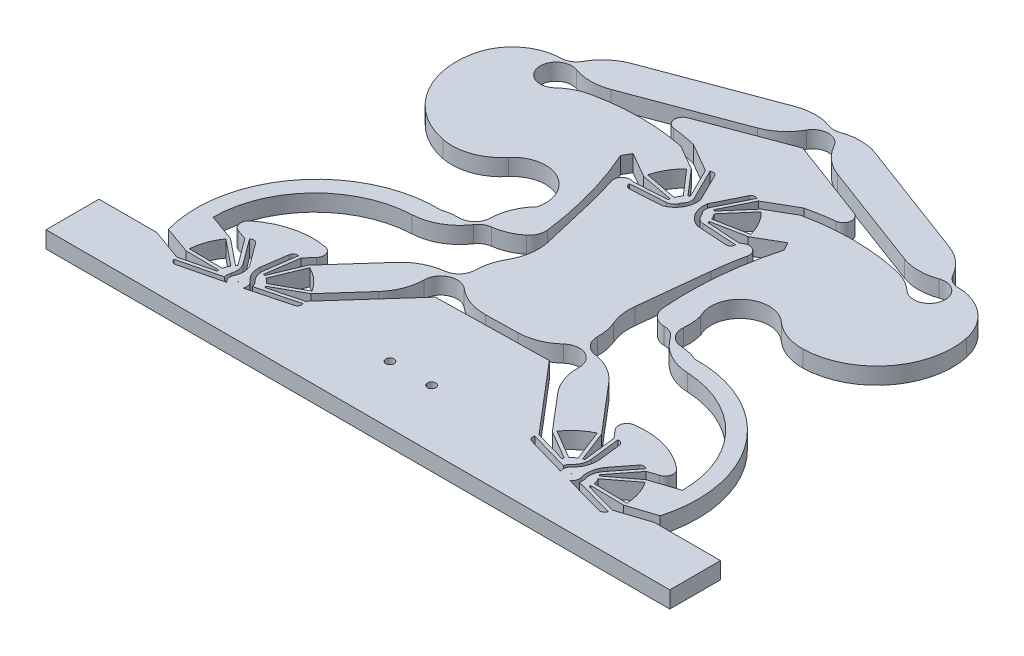
SolidWorks part; units mm, degrees
ref_plane "Front Plane" through (0, 0, 0) normal (0, 0, 1) x (1, 0, 0)
ref_plane "Top Plane" through (0, 0, 0) normal (0, 1, 0) x (1, 0, 0)
ref_plane "Right Plane" through (0, 0, 0) normal (1, 0, 0) x (0, 0, -1)
sketch "Sketch1" plane through (0, 0, 0) normal (0, 1, 0) x (1, 0, 0)
  line L1 (150, 150) -> (-150, 150)
  line L2 (150, 150) -> (150, -150)
  line L3 (150, -150) -> (-150, -150)
  line L4 (-150, 150) -> (-150, -150)
  line L5 (150, 150) -> (-150, -150) construction
  line L6 (150, -150) -> (-150, 150) construction
  point P0 (0, 0)
  dimension "D1" = 300
  dimension "D2" = 300
extrude "Boss-Extrude1" add sketch "Sketch1" along normal blind 10
sketch "Sketch6" plane through (0, 10, 0) normal (0, 1, 0) x (1, 0, 0)
  line L1 (150, 150) -> (187.3693, 150)
  line L2 (150, 150) -> (150, -150)
  line L3 (150, -150) -> (187.3693, -150)
  line L4 (187.3693, 150) -> (187.3693, -150)
extrude "Boss-Extrude2" add sketch "Sketch6" against normal blind 10
sketch "Sketch11" plane through (0, 10, 0) normal (0, 1, 0) x (1, 0, 0)
  line L1 (-150, -150) -> (-230.9434, -150)
  line L2 (-150, -150) -> (-150, 150)
  line L3 (-150, 150) -> (-230.9434, 150)
  line L4 (-230.9434, -150) -> (-230.9434, 150)
extrude "Boss-Extrude3" add sketch "Sketch11" against normal blind 10
sketch "Sketch2" plane through (0, 10, 0) normal (0, 1, 0) x (1, 0, 0)
  line L0 (-102.598, -119.2289) -> (-25.1328, -32.577) construction
  line L1 (-91.6465, -114.3232) -> (-72.2867, -109.3035)
  line L2 (-95.822, -117.472) -> (-71.6953, -111.2163)
  line L3 (-97.9731, -121.129) -> (-73.4342, -114.7664)
  line L4 (-92.1087, -113.4002) -> (-74.6265, -103.6856)
  line L5 (-93.2268, -111.7335) -> (-75.6526, -101.9678)
  line L6 (-74.6265, -103.6856) -> (-63.0561, -90.7431)
  line L7 (-72.2867, -109.3035) -> (-58.9642, -94.4011)
  line L8 (-58.9642, -94.4011) -> (-63.0561, -90.7431)
  line L9 (-82.795, -73.0969) -> (-78.7031, -76.755)
  line L10 (-96.1175, -87.9993) -> (-82.795, -73.0969)
  line L11 (-90.2735, -89.6975) -> (-78.7031, -76.755)
  line L12 (-96.1952, -109.0798) -> (-88.4519, -90.5255)
  line L13 (-97.9763, -108.1546) -> (-90.2735, -89.6975)
  line L14 (-105.0023, -114.8449) -> (-101.4181, -89.7493)
  line L15 (-101.6083, -112.2992) -> (-98.0843, -87.625)
  line L16 (-98.9452, -107.7984) -> (-96.1175, -87.9993)
  arc A0 (-105.0023, -114.8449) -> (-97.9731, -121.129) centre (-102.598, -119.2289) cw
  arc A1 (-97.9326, -114.0103) -> (-95.822, -117.472) centre (-102.598, -119.2289) cw
  arc A2 (-71.6953, -111.2163) -> (-73.4342, -114.7664) centre (-74.3398, -112.1219) cw
  arc A3 (-96.1952, -109.0798) -> (-93.2268, -111.7335) centre (-102.598, -119.2289) cw
  circle A4 centre (-102.598, -119.2289) radius 0.1
  arc A5 (-75.6526, -101.9678) -> (-88.4519, -90.5255) centre (-102.598, -119.2289) ccw
  arc A8 (-92.1087, -113.4002) -> (-91.6465, -114.3232) centre (-102.598, -119.2289) cw
  arc A9 (-97.9763, -108.1546) -> (-98.9452, -107.7984) centre (-102.598, -119.2289) ccw
  arc A11 (-98.0843, -87.625) -> (-101.4181, -89.7493) centre (-98.6891, -90.3541) ccw
  arc A12 (-97.9326, -114.0103) -> (-101.6083, -112.2992) centre (-102.598, -119.2289) ccw
  point P0 (-102.598, -119.2289)
  point P12 (0, -128.9646)
  point P13 (10.2845, -122.7817)
  point P14 (11.9871, -129.5203)
  point P15 (0, -128.9646)
  point P17 (11.9871, -129.5203)
  point P19 (-74.6265, -103.6856)
  dimension "D3" = 7
  dimension "D9" = 20
  dimension "D1" = 3
  dimension "D6" = 20
  dimension "D7" = 2
  dimension "D8" = 2
extrude "Cut-Extrude1" cut sketch "Sketch2" against normal blind 10
sketch "Sketch7" plane through (0, 10, 0) normal (0, 1, 0) x (1, 0, 0)
  line L0 (97.402, -119.2289) -> (22.065, -30.7204) construction
  line L1 (94.028, -107.713) -> (91.6822, -87.8511)
  line L2 (96.581, -112.2772) -> (93.6575, -87.5247)
  line L3 (99.9121, -114.9047) -> (96.9388, -89.7294)
  line L4 (93.0508, -108.0456) -> (85.7987, -89.4067)
  line L5 (91.2477, -108.9272) -> (83.9575, -90.1903)
  line L6 (85.7987, -89.4067) -> (74.5462, -76.1869)
  line L7 (91.6822, -87.8511) -> (78.7257, -72.6294)
  line L8 (78.7257, -72.6294) -> (74.5462, -76.1869)
  line L9 (54.3844, -93.3483) -> (58.5639, -89.7907)
  line L10 (67.3408, -108.57) -> (54.3844, -93.3483)
  line L11 (69.8164, -103.0106) -> (58.5639, -89.7907)
  line L12 (88.2158, -111.508) -> (70.884, -101.3182)
  line L13 (87.0574, -113.147) -> (69.8164, -103.0106)
  line L14 (92.7323, -121.016) -> (68.3553, -114.0592)
  line L15 (90.6708, -117.3079) -> (66.7031, -110.4679)
  line L16 (86.573, -114.0586) -> (67.3408, -108.57)
  circle A0 centre (-102.598, -119.2289) radius 0.1 construction
  arc A1 (92.7323, -121.016) -> (99.9121, -114.9047) centre (97.402, -119.2289) cw
  arc A2 (92.8648, -113.8985) -> (96.581, -112.2772) centre (97.402, -119.2289) cw
  arc A3 (93.6575, -87.5247) -> (96.9388, -89.7294) centre (94.1958, -90.2676) cw
  arc A4 (88.2158, -111.508) -> (91.2477, -108.9272) centre (97.402, -119.2289) cw
  circle A5 centre (97.402, -119.2289) radius 0.1
  arc A6 (83.9575, -90.1903) -> (70.884, -101.3182) centre (97.402, -119.2289) ccw
  arc A7 (93.0508, -108.0456) -> (94.028, -107.713) centre (97.402, -119.2289) cw
  arc A8 (87.0574, -113.147) -> (86.573, -114.0586) centre (97.402, -119.2289) ccw
  arc A9 (66.7031, -110.4679) -> (68.3553, -114.0592) centre (69.3248, -111.4374) ccw
  arc A10 (92.8648, -113.8985) -> (90.6708, -117.3079) centre (97.402, -119.2289) ccw
  point P0 (97.402, -119.2289)
  point P3 (97.402, -119.2289)
  point P15 (85.7987, -89.4067)
  dimension "D1" = 200
extrude "Cut-Extrude5" cut sketch "Sketch7" against normal blind 10
sketch "Sketch9" plane through (0, 10, 0) normal (0, 1, 0) x (1, 0, 0)
  line L0 (-4.298, 51.3626) -> (-4.2901, -64.8674) construction
  line L1 (-9.1923, 40.406) -> (-20.2788, 23.76)
  line L2 (-8.1783, 45.5365) -> (-21.9946, 24.7917)
  line L3 (-9.0122, 49.6964) -> (-23.0645, 28.5973)
  line L4 (-8.2325, 40.0259) -> (-14.79, 21.1315)
  line L5 (-6.288, 39.5287) -> (-12.88, 20.5348)
  line L6 (-14.79, 21.1315) -> (-14.7888, 3.7711)
  line L7 (-20.2788, 23.76) -> (-20.2774, 3.7708)
  line L8 (-20.2774, 3.7708) -> (-14.7888, 3.7711)
  line L9 (11.6878, 3.7729) -> (6.1992, 3.7726)
  line L10 (11.6865, 23.7622) -> (11.6878, 3.7729)
  line L11 (6.198, 21.1329) -> (6.1992, 3.7726)
  line L12 (-2.3064, 39.529) -> (4.2882, 20.536)
  line L13 (-0.362, 40.0265) -> (6.198, 21.1329)
  line L14 (0.4164, 49.697) -> (14.4715, 28.5999)
  line L15 (-0.417, 45.537) -> (13.4022, 24.7941)
  line L16 (0.5977, 40.4067) -> (11.6865, 23.7622)
  arc A0 (0.4164, 49.697) -> (-9.0122, 49.6964) centre (-4.298, 51.3626) cw
  arc A2 (-4.2975, 44.3626) -> (-8.1783, 45.5365) centre (-4.298, 51.3626) cw
  arc A3 (-21.9946, 24.7917) -> (-23.0645, 28.5973) centre (-20.6267, 27.2295) cw
  arc A4 (-2.3064, 39.529) -> (-6.288, 39.5287) centre (-4.298, 51.3626) cw
  circle A5 centre (-4.298, 51.3626) radius 0.1
  arc A6 (-12.88, 20.5348) -> (4.2882, 20.536) centre (-4.298, 51.3626) ccw
  arc A7 (-8.2325, 40.0259) -> (-9.1923, 40.406) centre (-4.298, 51.3626) cw
  arc A8 (-0.362, 40.0265) -> (0.5977, 40.4067) centre (-4.298, 51.3626) ccw
  arc A9 (13.4022, 24.7941) -> (14.4715, 28.5999) centre (12.034, 27.2317) ccw
  arc A10 (-4.2975, 44.3626) -> (-0.417, 45.537) centre (-4.298, 51.3626) ccw
  point P1 (-4.298, 51.3626)
  point P6 (-4.298, 51.3626)
  point P14 (-14.79, 21.1315)
extrude "Cut-Extrude7" cut sketch "Sketch9" against normal blind 10
sketch "Sketch8" plane through (0, 10, 0) normal (0, 1, 0) x (1, 0, 0)
  line L0 (-78.7031, -76.755) -> (-54.1381, -49.2767)
  line L1 (-82.795, -73.0969) -> (-20.2788, -3.1667)
  line L2 (54.3844, -93.3483) -> (31.8171, -66.8354)
  line L3 (58.5639, -89.7907) -> (40.7844, -68.9027)
  line L4 (74.5462, -76.1869) -> (50.3154, -47.7198)
  line L5 (78.7257, -72.6294) -> (11.6865, 6.1307)
  line L6 (-63.0561, -90.7431) -> (-44.4632, -69.9452)
  line L7 (-58.9642, -94.4011) -> (-35.4517, -68.1002)
  line L8 (78.7257, -72.6294) -> (74.5462, -76.1869) construction
  line L9 (58.5639, -89.7907) -> (54.3844, -93.3483) construction
  line L10 (-58.9642, -94.4011) -> (-63.0561, -90.7431) construction
  line L11 (-78.7031, -76.755) -> (-82.795, -73.0969) construction
  line L12 (78.7257, -72.6294) -> (74.5462, -76.1869)
  line L13 (58.5639, -89.7907) -> (54.3844, -93.3483)
  line L14 (-58.9642, -94.4011) -> (-63.0561, -90.7431)
  line L15 (-78.7031, -76.755) -> (-82.795, -73.0969)
  line L16 (-102.598, -119.3289) -> (-42.6146, -52.232) construction
  line L17 (97.502, -119.2289) -> (39.1666, -50.6944) construction
  line L18 (-63.0561, -90.7431) -> (-74.6265, -103.6856) construction
  line L19 (69.8164, -103.0106) -> (58.5639, -89.7907) construction
  line L20 (-42.6146, -52.232) -> (39.1666, -50.6944) construction
  line L21 (-27.7984, -62.4553) -> (24.3044, -61.4757)
  line L22 (-35.4517, -68.1002) -> (31.8171, -66.8354)
  line L23 (-42.4172, -62.7302) -> (39.364, -61.1926) construction
  line L24 (-82.795, -73.0969) -> (-96.1175, -87.9993) construction
  line L25 (-42.3138, -68.2292) -> (39.4673, -66.6916) construction
  line L26 (-90.2735, -89.6975) -> (-78.7031, -76.755) construction
  line L27 (91.6822, -87.8511) -> (78.7257, -72.6294) construction
  line L28 (-20.2788, -3.1667) -> (-20.2774, 3.7708)
  line L29 (-20.2774, 3.7708) -> (-14.7888, 3.7711)
  line L30 (-14.7888, 3.7711) -> (-14.79, -5.2622)
  line L31 (6.1992, 4.1095) -> (11.6865, 6.1307)
  line L32 (-47.4733, -41.8215) -> (43.8337, -40.1048) construction
  line L33 (-40.8084, -34.3663) -> (-14.79, -5.2622)
  line L34 (37.352, -32.4899) -> (6.1992, 4.1095)
  circle A0 centre (-102.598, -119.2289) radius 0.1 construction
  circle A1 centre (97.402, -119.2289) radius 0.1 construction
  arc A2 (-44.4632, -69.9452) -> (-27.7984, -62.4553) centre (-37.7984, -62.49) cw
  arc A3 (40.7844, -68.9027) -> (24.3044, -61.4757) centre (34.3026, -61.2877) ccw
  arc A4 (-40.8084, -34.3663) -> (-54.1381, -49.2767) centre (-47.4733, -41.8215) cw
  arc A5 (50.3154, -47.7198) -> (37.352, -32.4899) centre (43.8337, -40.1048) cw
  dimension "D5" = 10
  dimension "D6" = 10
  dimension "D8" = 10
  dimension "D9" = 10
  dimension "D1" = 90
  dimension "D2" = 90
  dimension "D7" = 10.5
  dimension "D3" = 10.5
  dimension "D4" = 16
extrude "Cut-Extrude6" cut sketch "Sketch8" against normal blind 10
sketch "Sketch10" plane through (0, 10, 0) normal (0, 1, 0) x (1, 0, 0)
  line L0 (-102.598, -119.2289) -> (-211.9592, -79.8648) construction
  line L1 (-111.2489, -110.9126) -> (-123.1554, -94.8429)
  line L2 (-106.7653, -113.6045) -> (-121.6035, -93.578)
  line L3 (-102.5688, -114.229) -> (-117.6605, -93.8604)
  line L4 (-111.9317, -111.6869) -> (-127.4878, -99.1168)
  line L5 (-113.0581, -113.348) -> (-128.6962, -100.7118)
  line L6 (-127.4878, -99.1168) -> (-143.8223, -93.2373)
  line L7 (-123.1554, -94.8429) -> (-141.9634, -88.0731)
  line L8 (-141.9634, -88.0731) -> (-143.8223, -93.2373)
  line L9 (-152.7892, -118.1493) -> (-150.9303, -112.985)
  line L10 (-133.9812, -124.9191) -> (-152.7892, -118.1493)
  line L11 (-134.5959, -118.8645) -> (-150.9303, -112.985)
  line L12 (-114.4066, -117.0943) -> (-134.5106, -116.8653)
  line L13 (-114.5972, -119.0923) -> (-134.5959, -118.8645)
  line L14 (-105.7621, -123.1004) -> (-130.373, -129.1782)
  line L15 (-109.3938, -120.9072) -> (-133.5915, -126.8829)
  line L16 (-114.5646, -120.124) -> (-133.9812, -124.9191)
  line L17 (97.402, -119.2289) -> (207.8148, -82.9187) construction
  line L18 (109.3391, -120.4562) -> (128.615, -125.7889)
  line L19 (104.1486, -121.0954) -> (128.1709, -127.7412)
  line L20 (100.4573, -123.1869) -> (124.8898, -129.9462)
  line L21 (109.4004, -119.4257) -> (129.3977, -119.7537)
  line L22 (109.2654, -117.4232) -> (129.368, -117.753)
  line L23 (129.3977, -119.7537) -> (145.8892, -114.3304)
  line L24 (128.615, -125.7889) -> (147.6038, -119.5443)
  line L25 (147.6038, -119.5443) -> (145.8892, -114.3304)
  line L26 (137.6179, -89.1789) -> (139.3326, -94.3928)
  line L27 (118.6291, -95.4235) -> (137.6179, -89.1789)
  line L28 (122.8411, -99.8162) -> (139.3326, -94.3928)
  line L29 (108.0215, -113.6409) -> (124.0046, -101.4441)
  line L30 (106.9417, -111.9491) -> (122.8411, -99.8162)
  line L31 (97.5118, -114.2301) -> (113.1636, -94.2888)
  line L32 (101.724, -113.7225) -> (117.1129, -94.116)
  line L33 (106.2807, -111.1562) -> (118.6291, -95.4235)
  arc A0 (-105.7621, -123.1004) -> (-102.5688, -114.229) centre (-102.598, -119.2289) cw
  arc A1 (-109.1843, -116.8582) -> (-106.7653, -113.6045) centre (-102.598, -119.2289) cw
  arc A2 (-121.6035, -93.578) -> (-117.6605, -93.8604) centre (-119.7732, -95.6907) cw
  arc A3 (-114.4066, -117.0943) -> (-113.0581, -113.348) centre (-102.598, -119.2289) cw
  circle A4 centre (-102.598, -119.2289) radius 0.1
  arc A5 (-128.6962, -100.7118) -> (-134.5106, -116.8653) centre (-102.598, -119.2289) ccw
  arc A6 (-111.9317, -111.6869) -> (-111.2489, -110.9126) centre (-102.598, -119.2289) cw
  arc A7 (-114.5972, -119.0923) -> (-114.5646, -120.124) centre (-102.598, -119.2289) ccw
  arc A8 (-133.5915, -126.8829) -> (-130.373, -129.1782) centre (-130.8346, -126.4213) ccw
  arc A9 (-109.1843, -116.8582) -> (-109.3938, -120.9072) centre (-102.598, -119.2289) ccw
  arc A10 (97.5118, -114.2301) -> (100.4573, -123.1869) centre (97.402, -119.2289) cw
  arc A11 (104.0517, -117.0421) -> (104.1486, -121.0954) centre (97.402, -119.2289) cw
  arc A12 (128.1709, -127.7412) -> (124.8898, -129.9462) centre (125.4278, -127.2031) cw
  arc A13 (108.0215, -113.6409) -> (109.2654, -117.4232) centre (97.402, -119.2289) cw
  circle A14 centre (97.402, -119.2289) radius 0.1
  arc A15 (129.368, -117.753) -> (124.0046, -101.4441) centre (97.402, -119.2289) ccw
  arc A16 (109.4004, -119.4257) -> (109.3391, -120.4562) centre (97.402, -119.2289) cw
  arc A17 (106.9417, -111.9491) -> (106.2807, -111.1562) centre (97.402, -119.2289) ccw
  arc A18 (117.1129, -94.116) -> (113.1636, -94.2888) centre (115.2247, -96.177) ccw
  arc A19 (104.0517, -117.0421) -> (101.724, -113.7225) centre (97.402, -119.2289) ccw
  point P0 (-102.598, -119.2289)
  point P12 (-127.4878, -99.1168)
  point P33 (-102.598, -119.2289)
  point P34 (97.402, -119.2289)
  point P36 (97.402, -119.2289)
  point P50 (129.3977, -119.7537)
extrude "Cut-Extrude8" cut sketch "Sketch10" against normal blind 10
sketch "Sketch12" plane through (0, 10, 0) normal (0, 1, 0) x (1, 0, 0)
  line L0 (-4.298, 51.3626) -> (96.3562, 109.4844) construction
  line L1 (7.6378, 52.6023) -> (27.5969, 51.3241)
  line L2 (2.6877, 50.9152) -> (27.5613, 49.3223)
  line L3 (1.8219, 47.9645) -> (24.8005, 46.493)
  line L4 (7.4871, 53.6236) -> (27.1289, 57.3919)
  line L5 (6.9454, 55.5561) -> (26.6906, 59.3442)
  line L6 (27.1289, 57.3919) -> (42.1628, 66.073)
  line L7 (27.5969, 51.3241) -> (44.9074, 61.3199)
  line L8 (44.9074, 61.3199) -> (42.1628, 66.073)
  line L9 (28.9229, 89.0016) -> (31.6676, 84.2485)
  line L10 (11.6124, 79.0058) -> (28.9229, 89.0016)
  line L11 (16.6336, 75.5673) -> (31.6676, 84.2485)
  line L12 (4.9544, 59.0042) -> (18.1055, 74.2117)
  line L13 (3.5514, 60.4393) -> (16.6336, 75.5673)
  line L14 (-3.8645, 59.0029) -> (6.0303, 78.9989)
  line L15 (-0.9513, 58.1259) -> (9.8609, 79.9756)
  line L16 (2.7422, 61.0804) -> (11.6124, 79.0058)
  line L17 (-4.298, 51.3626) -> (-104.9601, 109.4708) construction
  line L18 (-11.3395, 61.0794) -> (-20.2122, 79.0036)
  line L19 (-7.9071, 58.6536) -> (-18.4608, 79.9737)
  line L20 (-4.7326, 59.0029) -> (-14.6301, 78.9975)
  line L21 (-12.1486, 60.4383) -> (-25.2329, 75.5644)
  line L22 (-13.5514, 59.0029) -> (-26.7046, 74.2087)
  line L23 (-25.2329, 75.5644) -> (-40.268, 84.2436)
  line L24 (-20.2122, 79.0036) -> (-37.5241, 88.9971)
  line L25 (-37.5241, 88.9971) -> (-40.268, 84.2436)
  line L26 (-53.5048, 61.3133) -> (-50.7608, 66.0668)
  line L27 (-36.1929, 51.3198) -> (-53.5048, 61.3133)
  line L28 (-35.7257, 57.3876) -> (-50.7608, 66.0668)
  line L29 (-15.542, 55.5546) -> (-35.2877, 59.34)
  line L30 (-16.0834, 53.622) -> (-35.7257, 57.3876)
  line L31 (-10.4175, 47.9637) -> (-33.3959, 46.489)
  line L32 (-11.2836, 50.9143) -> (-36.1571, 49.318)
  line L33 (-16.234, 52.6007) -> (-36.1929, 51.3198)
  line L34 (-5.7605, 61.0794) -> (-4.4152, 58.3616)
  line L35 (-8.0977, 57.2416) -> (-7.9071, 58.6536)
  line L36 (-0.9513, 58.1259) -> (-0.4979, 57.2413)
  line L37 (-3.8645, 59.0029) -> (-2.8369, 61.0794)
  line L38 (-2.8369, 61.0794) -> (-4.1818, 58.3616)
  arc A0 (-10.4175, 47.9637) -> (1.8219, 47.9645) centre (-4.298, 51.3626) ccw
  arc A1 (-8.0977, 57.2416) -> (-11.2836, 50.9143) centre (-4.298, 51.3626) ccw
  arc A2 (27.5613, 49.3223) -> (24.8005, 46.493) centre (24.7663, 49.2881) cw
  arc A3 (4.9544, 59.0042) -> (6.9454, 55.5561) centre (-4.298, 51.3626) cw
  circle A4 centre (-4.298, 51.3626) radius 0.1
  arc A5 (26.6906, 59.3442) -> (18.1055, 74.2117) centre (-4.298, 51.3626) ccw
  arc A6 (7.4871, 53.6236) -> (7.6378, 52.6023) centre (-4.298, 51.3626) cw
  arc A7 (3.5514, 60.4393) -> (2.7422, 61.0804) centre (-4.298, 51.3626) ccw
  arc A8 (9.8609, 79.9756) -> (6.0303, 78.9989) centre (8.434, 77.572) ccw
  arc A9 (-4.1818, 58.3616) -> (-4.4152, 58.3616) centre (-4.298, 51.3626) ccw
  arc A10 (2.6877, 50.9152) -> (-0.4979, 57.2413) centre (-4.298, 51.3626) ccw
  arc A12 (-18.4608, 79.9737) -> (-14.6301, 78.9975) centre (-17.0336, 77.5703) cw
  arc A13 (-15.542, 55.5546) -> (-13.5514, 59.0029) centre (-4.298, 51.3626) cw
  circle A14 centre (-4.298, 51.3626) radius 0.1
  arc A15 (-26.7046, 74.2087) -> (-35.2877, 59.34) centre (-4.298, 51.3626) ccw
  arc A16 (-12.1486, 60.4383) -> (-11.3395, 61.0794) centre (-4.298, 51.3626) cw
  arc A17 (-16.0834, 53.622) -> (-16.234, 52.6007) centre (-4.298, 51.3626) ccw
  arc A18 (-36.1571, 49.318) -> (-33.3959, 46.489) centre (-33.362, 49.2841) ccw
  point P0 (-4.298, 51.3626)
  point P1 (-4.298, 51.3626)
  point P14 (27.1289, 57.3919)
  point P35 (-4.298, 51.3626)
  point P47 (-25.2329, 75.5644)
extrude "Cut-Extrude10" cut sketch "Sketch12" against normal blind 10 contours L32 A18 L31 A0 L3 A2 L2 A10 L36 L15 A8 L14 L38 A9 L34 L20 A12 L19 L35 A1 A4 | A17 L30 L28 L26 L27 L33 | L22 A15 L29 A13 | L21 A16 L18 L24 L25 L23 | A7 L13 L11 L9 L10 L16 | L5 A5 L12 A3 | L4 A6 L1 L7 L8 L6
sketch "Sketch15" plane through (0, 10, 0) normal (0, 1, 0) x (1, 0, 0)
  line L0 (-102.698, -119.2289) -> (97.502, -119.2289) construction
  line L1 (-2.598, -119.2289) -> (-2.598, -35.5348) construction
  line L2 (56.4734, -17.1669) -> (97.502, -119.2289) construction
  line L3 (97.502, -119.2289) -> (76.6605, -94.8611) construction
  line L4 (56.4734, -17.1669) -> (107.0283, -76.2756) construction
  line L5 (39.421, -13.3837) -> (42.3191, -16.7722)
  line L6 (54.1502, 1.7037) -> (58.2781, -3.1226)
  line L7 (34.594, -16.2018) -> (54.0342, -38.9313)
  line L8 (57.9708, 5.6985) -> (79.2944, -19.2331)
  line L9 (56.4734, -17.1669) -> (107.3321, -76.6308) construction
  line L10 (44.3141, -27.5666) -> (95.1728, -87.0305) construction
  line L11 (48.4939, -23.9917) -> (99.3525, -83.4556) construction
  line L12 (64.4529, -10.3422) -> (115.3116, -69.806) construction
  line L13 (68.6326, -6.7673) -> (119.4913, -66.2312) construction
  line L14 (147.6038, -119.5443) -> (145.8892, -114.3304) construction
  line L15 (139.3326, -94.3928) -> (137.6179, -89.1789) construction
  line L16 (147.6038, -119.5443) -> (145.8892, -114.3304)
  line L17 (139.3326, -94.3928) -> (137.6179, -89.1789)
  line L18 (56.4734, -17.1669) -> (48.4939, -23.9917) construction
  line L19 (48.4939, -23.9917) -> (64.4529, -10.3422) construction
  line L20 (70.6277, -17.5617) -> (74.7555, -22.388)
  line L21 (54.6686, -31.2113) -> (57.5667, -34.5997)
  line L22 (34.594, -16.2018) -> (39.421, -13.3837)
  line L23 (57.9708, 5.6985) -> (54.1502, 1.7037)
  line L24 (-61.6693, -17.1669) -> (-102.698, -119.2289) construction
  line L25 (-71.4606, -28.1194) -> (-43.9237, 2.6832) construction
  line L26 (-90.2735, -89.6975) -> (-54.1381, -49.2767) construction
  line L27 (-63.6326, -35.1174) -> (-60.1729, -31.2474)
  line L28 (-79.2886, -21.1213) -> (-75.8289, -17.2513)
  line L29 (-63.1657, -3.0864) -> (-51.7517, 9.6813)
  line L30 (-47.5098, -17.0825) -> (-36.0957, -4.3149)
  line L31 (-79.2886, -21.1213) -> (-51.7517, 9.6813) construction
  line L32 (-59.5323, -38.7831) -> (-31.9953, -7.9805) construction
  line L33 (-59.8905, -39.1838) -> (-31.9953, -7.9805)
  line L34 (-83.3889, -17.4557) -> (-55.852, 13.3469)
  line L35 (-61.6693, -17.1669) -> (-53.8414, -24.165) construction
  line L36 (-53.8414, -24.165) -> (-69.4973, -10.1689) construction
  line L53 (-63.6326, -35.1174) -> (-36.0957, -4.3149) construction
  line L54 (-150.9303, -112.985) -> (-152.7892, -118.1493) construction
  line L55 (-141.9634, -88.0731) -> (-143.8223, -93.2373) construction
  line L56 (-150.9303, -112.985) -> (-152.7892, -118.1493)
  line L57 (-141.9634, -88.0731) -> (-143.8223, -93.2373)
  line L58 (-55.852, 13.3469) -> (-51.7517, 9.6813)
  line L59 (-36.0957, -4.3149) -> (-31.9953, -7.9805)
  circle A0 centre (-102.598, -119.2289) radius 0.1 construction
  circle A1 centre (97.402, -119.2289) radius 0.1 construction
  arc A2 (83.9575, -90.1903) -> (70.884, -101.3182) centre (97.402, -119.2289) ccw construction
  arc A3 (54.6686, -31.2113) -> (42.3191, -16.7722) centre (48.4939, -23.9917) ccw
  arc A4 (58.2781, -3.1226) -> (70.6277, -17.5617) centre (64.4529, -10.3422) ccw
  arc A5 (54.0342, -38.9313) -> (137.6179, -89.1789) centre (77.8655, -93.9314) cw
  arc A6 (57.5667, -34.5997) -> (139.3326, -94.3928) centre (76.6633, -94.2887) cw
  arc A7 (74.7555, -22.388) -> (145.8892, -114.3304) centre (76.5744, -94.4692) cw
  arc A8 (79.2944, -19.2331) -> (147.6038, -119.5443) centre (76.8134, -94.3367) cw
  arc A9 (-60.1729, -31.2474) -> (-47.5098, -17.0825) centre (-53.8414, -24.165) cw
  arc A10 (-75.8289, -17.2513) -> (-63.1657, -3.0864) centre (-69.4973, -10.1689) ccw
  arc A11 (-141.9634, -88.0731) -> (-59.8905, -39.1838) centre (-83.4314, -92.9991) cw
  arc A12 (-143.8223, -93.2373) -> (-63.6326, -35.1174) centre (-82.5525, -93.3931) cw
  arc A13 (-150.9303, -112.985) -> (-79.2886, -21.1213) centre (-81.1817, -93.5124) cw
  arc A14 (-152.7892, -118.1493) -> (-83.3889, -17.4557) centre (-81.045, -93.334) cw
  point P9 (56.4734, -17.1669)
  point P47 (-61.6693, -17.1669)
  dimension "D7" = 110
  dimension "D1" = 110
  dimension "D2" = 68.1
  dimension "D8" = 68.1
  dimension "D3" = 10.5
  dimension "D4" = 10.5
  dimension "D5" = 16
  dimension "D6" = 16
  dimension "D9" = 10.5
  dimension "D10" = 10.5
  dimension "D13" = 16
  dimension "D14" = 16
extrude "Cut-Extrude12" cut sketch "Sketch15" against normal blind 10
sketch "Sketch13" plane through (0, 10, 0) normal (0, 1, 0) x (1, 0, 0)
  line L0 (-102.598, -119.3289) -> (97.402, -119.3289) construction
  line L1 (-2.598, -119.3289) -> (-2.598, 136.8711) construction
  line L2 (-2.598, 136.8711) -> (106.2742, 96.1738) construction
  line L3 (5.9507, 128.4497) -> (17.66, 112.2357)
  line L4 (1.5003, 131.1962) -> (16.0927, 110.9899)
  line L5 (-2.598, 131.7469) -> (12.1535, 111.3205)
  line L6 (6.6429, 129.2156) -> (22.0443, 116.4564)
  line L7 (7.7895, 130.8628) -> (23.272, 118.0365)
  line L8 (22.0443, 116.4564) -> (38.3057, 110.3778)
  line L9 (17.66, 112.2357) -> (36.3839, 105.2366)
  line L10 (36.3839, 105.2366) -> (38.3057, 110.3778)
  line L11 (47.5763, 135.1783) -> (45.6545, 130.0371)
  line L12 (28.8524, 142.1774) -> (47.5763, 135.1783)
  line L13 (29.3931, 136.1158) -> (45.6545, 130.0371)
  line L14 (9.1837, 134.5924) -> (29.2833, 134.1178)
  line L15 (9.3987, 136.5878) -> (29.3931, 136.1158)
  line L16 (0.6132, 140.7036) -> (25.2965, 146.4803)
  line L17 (4.2178, 138.4662) -> (28.4867, 144.1459)
  line L18 (9.3786, 137.6199) -> (28.8524, 142.1774)
  line L35 (-2.598, 136.8711) -> (-111.4702, 96.1738) construction
  line L36 (-14.5746, 137.6199) -> (-34.0484, 142.1774)
  line L37 (-9.4138, 138.4662) -> (-33.6827, 144.1459)
  line L38 (-5.8091, 140.7036) -> (-30.4924, 146.4803)
  line L39 (-14.5946, 136.5878) -> (-34.5891, 136.1158)
  line L40 (-14.3796, 134.5924) -> (-34.4793, 134.1178)
  line L41 (-34.5891, 136.1158) -> (-50.8504, 130.0371)
  line L42 (-34.0484, 142.1774) -> (-52.7723, 135.1783)
  line L43 (-52.7723, 135.1783) -> (-50.8504, 130.0371)
  line L44 (-41.5798, 105.2366) -> (-43.5016, 110.3778)
  line L45 (-22.856, 112.2357) -> (-41.5798, 105.2366)
  line L46 (-27.2403, 116.4564) -> (-43.5016, 110.3778)
  line L47 (-12.9855, 130.8628) -> (-28.468, 118.0365)
  line L48 (-11.8388, 129.2156) -> (-27.2403, 116.4564)
  line L49 (-2.598, 131.7469) -> (-17.3494, 111.3205)
  line L50 (-6.6962, 131.1962) -> (-21.2887, 110.9899)
  line L51 (-11.1467, 128.4497) -> (-22.856, 112.2357)
  circle A0 centre (-102.598, -119.2289) radius 0.1 construction
  circle A1 centre (97.402, -119.2289) radius 0.1 construction
  arc A2 (0.6132, 140.7036) -> (-5.8091, 140.7036) centre (-2.598, 136.8711) cw
  arc A3 (4.2178, 138.4662) -> (1.5003, 131.1962) centre (-2.598, 136.8711) cw
  arc A4 (16.0927, 110.9899) -> (12.1535, 111.3205) centre (14.2884, 113.1248) cw
  arc A5 (9.1837, 134.5924) -> (7.7895, 130.8628) centre (-2.598, 136.8711) cw
  circle A6 centre (-2.598, 136.8711) radius 0.1
  arc A7 (23.272, 118.0365) -> (29.2833, 134.1178) centre (-2.598, 136.8711) ccw
  arc A8 (6.6429, 129.2156) -> (5.9507, 128.4497) centre (-2.598, 136.8711) cw
  arc A9 (9.3987, 136.5878) -> (9.3786, 137.6199) centre (-2.598, 136.8711) ccw
  arc A10 (28.4867, 144.1459) -> (25.2965, 146.4803) centre (25.7244, 143.718) ccw
  arc A16 (-33.6827, 144.1459) -> (-30.4924, 146.4803) centre (-30.9203, 143.718) cw
  arc A17 (-14.5946, 136.5878) -> (-14.5746, 137.6199) centre (-2.598, 136.8711) cw
  arc A18 (-11.8388, 129.2156) -> (-11.1467, 128.4497) centre (-2.598, 136.8711) ccw
  arc A19 (-21.2887, 110.9899) -> (-17.3494, 111.3205) centre (-19.4844, 113.1248) ccw
  arc A20 (-6.6962, 131.1962) -> (-9.4138, 138.4662) centre (-2.598, 136.8711) cw
  arc A24 (-28.468, 118.0365) -> (-34.4793, 134.1178) centre (-2.598, 136.8711) cw
  arc A25 (-14.3796, 134.5924) -> (-12.9855, 130.8628) centre (-2.598, 136.8711) ccw
  point P8 (-2.598, 136.8711)
  point P20 (22.0443, 116.4564)
  dimension "D1" = 256.2
sketch "Sketch16" plane through (0, 10, 0) normal (0, 1, 0) x (1, 0, 0)
  line L0 (-102.698, -119.2289) -> (97.502, -119.2289) construction
  line L1 (-2.598, -119.2289) -> (-2.598, 136.9711) construction
  line L2 (-2.598, 136.9711) -> (113.2684, 93.6504) construction
  line L3 (-2.598, 136.9711) -> (-118.4643, 93.6504) construction
  line L4 (-2.598, 119.8893) -> (-77.1316, 92.0224)
  line L5 (-2.598, 119.8893) -> (71.3148, 92.2545)
  line L6 (-2.598, 154.0528) -> (-124.0677, 108.6372)
  line L7 (-2.598, 154.0528) -> (118.8717, 108.6372)
  line L8 (6.3004, 144.854) -> (108.0472, 106.8125)
  line L9 (-11.4964, 144.854) -> (-113.2431, 106.8125)
  line L10 (6.3004, 122.4342) -> (100.6928, 87.1423)
  line L11 (-11.4964, 122.4342) -> (-105.8888, 87.1423)
  line L12 (113.2684, 93.6504) -> (107.665, 78.6637) construction
  line L13 (107.665, 78.6637) -> (118.8717, 108.6372) construction
  line L14 (-118.4643, 93.6504) -> (-112.861, 78.6637) construction
  line L15 (-112.861, 78.6637) -> (-124.0677, 108.6372) construction
  line L16 (28.9229, 89.0016) -> (31.6676, 84.2485) construction
  line L17 (-2.598, 119.8893) -> (107.665, 78.6637) construction
  line L18 (-2.598, 119.8893) -> (-112.861, 78.6637) construction
  line L19 (-37.5241, 88.9971) -> (-40.268, 84.2436) construction
  line L20 (57.9708, 5.6985) -> (54.1502, 1.7037) construction
  line L21 (39.421, -13.3837) -> (34.594, -16.2018) construction
  line L22 (-31.9953, -7.9805) -> (-36.0957, -4.3149) construction
  line L23 (-51.7517, 9.6813) -> (-55.852, 13.3469) construction
  line L24 (44.9074, 61.3199) -> (42.1628, 66.073) construction
  line L25 (-53.5048, 61.3133) -> (-50.7608, 66.0668) construction
  line L26 (28.9229, 89.0016) -> (31.6676, 84.2485)
  line L27 (-37.5241, 88.9971) -> (-40.268, 84.2436)
  line L28 (57.9708, 5.6985) -> (54.1502, 1.7037)
  line L29 (39.421, -13.3837) -> (34.594, -16.2018)
  line L30 (-31.9953, -7.9805) -> (-36.0957, -4.3149)
  line L31 (-51.7517, 9.6813) -> (-55.852, 13.3469)
  line L32 (44.9074, 61.3199) -> (42.1628, 66.073)
  line L33 (-53.5048, 61.3133) -> (-50.7608, 66.0668)
  line L37 (-2.598, 148.181) -> (-122.1415, 103.4855) construction
  line L38 (-2.598, 148.181) -> (116.9455, 103.4855) construction
  line L39 (-2.598, 125.7612) -> (-114.7872, 83.8154) construction
  line L40 (-2.598, 125.7612) -> (109.5912, 83.8154) construction
  circle A0 centre (-102.598, -119.2289) radius 0.1 construction
  circle A1 centre (97.402, -119.2289) radius 0.1 construction
  arc A2 (118.8717, 108.6372) -> (82.7532, 12.0339) centre (100.8124, 60.3356) cw
  arc A3 (125.4479, 99.2476) -> (85.0812, 18.2603) centre (101.0134, 60.8729) cw
  arc A4 (85.0812, 18.2603) -> (54.1502, 1.7037) centre (69.6157, 9.982) ccw
  arc A5 (82.7532, 12.0339) -> (57.9708, 5.6985) centre (70.362, 8.8662) ccw
  arc A6 (-130.6439, 99.2476) -> (-90.2771, 18.2603) centre (-106.2093, 60.8729) ccw
  arc A7 (-124.0677, 108.6372) -> (-87.9492, 12.0339) centre (-106.0084, 60.3356) ccw
  arc A8 (-90.2771, 18.2603) -> (-51.7517, 9.6813) centre (-71.0144, 13.9708) cw
  arc A9 (-87.9492, 12.0339) -> (-55.852, 13.3469) centre (-71.9006, 12.6904) cw
  arc A10 (28.9229, 89.0016) -> (71.3148, 92.2545) centre (60.6799, -47.0037) cw
  arc A11 (31.6676, 84.2485) -> (100.4807, 81.1231) centre (60.1153, -48.514) cw
  arc A12 (-37.5241, 88.9971) -> (-77.1316, 92.0224) centre (-67.4997, -42.6608) ccw
  arc A13 (-40.268, 84.2436) -> (-105.6791, 81.1146) centre (-66.9014, -44.261) ccw
  arc A14 (-53.5048, 61.3133) -> (-36.0957, -4.3149) centre (-250.3297, -26.0213) cw
  arc A15 (-31.9953, -7.9805) -> (-50.7608, 66.0668) centre (-276.9588, -30.659) ccw
  arc A16 (42.1628, 66.073) -> (34.594, -16.2018) centre (213.104, 8.8619) ccw
  arc A17 (44.9074, 61.3199) -> (39.421, -13.3837) centre (230.2328, 10.1558) ccw
  arc A18 (6.3004, 122.4342) -> (-11.4964, 122.4342) centre (-2.598, 125.7612) ccw
  arc A19 (-11.4964, 144.854) -> (6.3004, 144.854) centre (-2.598, 148.181) ccw
  arc A20 (-113.2431, 106.8125) -> (-130.6439, 99.2476) centre (-122.1415, 103.4855) cw
  arc A21 (-105.8888, 87.1423) -> (-105.6791, 81.1146) centre (-114.7872, 83.8154) ccw
  arc A22 (108.0472, 106.8125) -> (125.4479, 99.2476) centre (116.9455, 103.4855) ccw
  arc A23 (100.6928, 87.1423) -> (100.4807, 81.1231) centre (109.5912, 83.8154) cw
  dimension "D1" = 256.2
  dimension "D2" = 69.5
  dimension "D3" = 123.7
  dimension "D4" = 16
  dimension "D5" = 16
  dimension "D6" = 10.5
  dimension "D7" = 10.5
extrude "Cut-Extrude13" cut sketch "Sketch16" against normal blind 10
fillet "Fillet1" radius 30 16 edges at (-44.4632, 5, 69.9452) (-27.7984, 5, 62.4553) (40.7844, 5, 68.9027) (24.3044, 5, 61.4757) (50.3154, 5, 47.7198) (37.352, 5, 32.4899) (-40.8084, 5, 34.3663) (-54.1381, 5, 49.2767) (70.6277, 5, 17.5617) (-75.8289, 5, 17.2513) (58.2781, 5, 3.1226) (54.6686, 5, 31.2113) (42.3191, 5, 16.7722) (-60.1729, 5, 31.2474) (-47.5098, 5, 17.0825) (-63.1657, 5, 3.0864)
fillet "Fillet2" radius 30 14 edges at (57.5667, 5, 34.5997) (-63.6326, 5, 35.1174) (100.6928, 5, -87.1423) (6.3004, 5, -122.4342) (-11.4964, 5, -122.4342) (-105.8888, 5, -87.1423) (100.4807, 5, -81.1231) (125.4479, 5, -99.2476) (108.0472, 5, -106.8125) (6.3004, 5, -144.854) (-11.4964, 5, -144.854) (-105.6791, 5, -81.1146) (-113.2431, 5, -106.8125) (-130.6439, 5, -99.2476)
fillet "Fillet3" radius 30 2 edges at (-90.2771, 5, -18.2603) (85.0812, 5, -18.2603)
fillet "Fillet4" radius 10 2 edges at (-36.0957, 5, 4.3149) (39.421, 5, 13.3837)
sketch "Sketch17" plane through (0, 10, 0) normal (0, 1, 0) x (1, 0, 0)
  line L0 (-55.852, 13.3469) -> (-83.3889, -17.4557) construction
  line L1 (-13.4378, 150) -> (-124.0677, 108.6372) construction
  line L2 (79.2944, -19.2331) -> (57.9708, 5.6985) construction
  line L3 (118.8717, 108.6372) -> (8.2418, 150) construction
  line L4 (187.3693, -150) -> (187.3693, 150) construction
  line L5 (187.3693, 150) -> (8.2418, 150) construction
  line L7 (-13.4378, 150) -> (-230.9434, 150) construction
  line L8 (-55.852, 13.3469) -> (-83.3889, -17.4557)
  line L9 (-13.4378, 150) -> (-124.0677, 108.6372)
  line L10 (79.2944, -19.2331) -> (57.9708, 5.6985)
  line L11 (118.8717, 108.6372) -> (8.2418, 150)
  line L12 (187.3693, -119.5443) -> (187.3693, 150)
  line L13 (187.3693, 150) -> (8.2418, 150)
  line L14 (-230.9434, -118.1493) -> (-248.4685, -118.1493)
  line L15 (-13.4378, 150) -> (-248.4685, 150)
  line L16 (-152.7892, -118.1493) -> (-187.4899, -118.1493)
  line L17 (147.6038, -119.5443) -> (187.3693, -119.5443)
  line L18 (-248.4685, -118.1493) -> (-248.4685, 150)
  line L19 (-230.9434, -150) -> (-187.4899, -150)
  line L20 (-230.9434, -150) -> (-230.9434, -118.1493)
  line L22 (-187.4899, -150) -> (-187.4899, -118.1493)
  arc A0 (-83.3889, -17.4557) -> (-152.7892, -118.1493) centre (-81.045, -93.334) ccw construction
  arc A1 (-55.852, 13.3469) -> (-87.9492, 12.0339) centre (-71.9006, 12.6904) ccw construction
  arc A2 (-124.0677, 108.6372) -> (-87.9492, 12.0339) centre (-106.0084, 60.3356) ccw construction
  arc A3 (147.6038, -119.5443) -> (79.2944, -19.2331) centre (76.8134, -94.3367) ccw construction
  arc A4 (82.7532, 12.0339) -> (57.9708, 5.6985) centre (70.362, 8.8662) ccw construction
  arc A5 (82.7532, 12.0339) -> (118.8717, 108.6372) centre (100.8124, 60.3356) ccw construction
  arc A6 (-83.3889, -17.4557) -> (-152.7892, -118.1493) centre (-81.045, -93.334) ccw
  arc A7 (-55.852, 13.3469) -> (-87.9492, 12.0339) centre (-71.9006, 12.6904) ccw
  arc A8 (-124.0677, 108.6372) -> (-87.9492, 12.0339) centre (-106.0084, 60.3356) ccw
  arc A9 (147.6038, -119.5443) -> (79.2944, -19.2331) centre (76.8134, -94.3367) ccw
  arc A10 (82.7532, 12.0339) -> (57.9708, 5.6985) centre (70.362, 8.8662) ccw
  arc A11 (82.7532, 12.0339) -> (118.8717, 108.6372) centre (100.8124, 60.3356) ccw
extrude "Cut-Extrude14" cut sketch "Sketch17" against normal blind 10
sketch "Sketch18" plane through (0, 10, 0) normal (0, 1, 0) x (1, 0, 0)
  line L0 (34.594, -16.2018) -> (54.0342, -38.9313) construction
  line L1 (34.594, -16.2018) -> (54.0342, -38.9313)
  line L2 (56.445, -37.9484) -> (34.1728, -12.993)
  arc A0 (137.6179, -89.1789) -> (54.0342, -38.9313) centre (77.8655, -93.9314) ccw construction
  arc A1 (39.7702, 58.3535) -> (34.594, -16.2018) centre (213.104, 8.8619) ccw construction
  arc A2 (56.445, -37.9484) -> (54.0342, -38.9313) centre (77.8655, -93.9314) ccw
  arc A3 (34.1728, -12.993) -> (34.594, -16.2018) centre (213.104, 8.8619) ccw
extrude "Boss-Extrude4" add sketch "Sketch18" against normal blind 10
sketch "Sketch20" plane through (0, 10, 0) normal (0, 1, 0) x (1, 0, 0)
  line L0 (-10.3008, 47.7616) -> (-23.0645, 28.5973) construction
  line L1 (14.4715, 28.5999) -> (1.7052, 47.7624) construction
  line L3 (1.8219, 47.9645) -> (24.8005, 46.493) construction
  line L4 (-4.1818, 58.3616) -> (6.0303, 78.9989) construction
  line L5 (-14.6301, 78.9975) -> (-4.4152, 58.3616) construction
  line L6 (-10.4175, 47.9637) -> (-33.3959, 46.489) construction
  line L7 (-9.5226, 68.6795) -> (0.9242, 68.6802)
  line L8 (13.3112, 47.2288) -> (8.0884, 38.1812)
  line L9 (-16.6826, 38.1795) -> (-21.9067, 47.2264)
  arc A0 (-16.6826, 38.1795) -> (8.0884, 38.1812) centre (-4.2969, 34.2307) cw
  arc A1 (13.3112, 47.2288) -> (0.9242, 68.6802) centre (10.5875, 59.9581) cw
  arc A2 (-9.5226, 68.6795) -> (-21.9067, 47.2264) centre (-19.2255, 59.9796) cw
extrude "Boss-Extrude5" add sketch "Sketch20" against normal blind 10
fillet "Fillet7" radius 5 6 edges at (-8.0977, 5, -57.2416) (-0.4979, 5, -57.2413) (-11.2836, 5, -50.9143) (2.6877, 5, -50.9152) (-0.417, 5, -45.537) (-8.1783, 5, -45.5365)
fillet "Fillet8" radius 5 2 edges at (-0.9513, 5, -58.1259) (-7.9071, 5, -58.6536)
sketch "Sketch21" plane through (0, 10, 0) normal (0, 1, 0) x (1, 0, 0)
  line L0 (91.6822, -87.8511) -> (11.6877, 6.1293) construction
  line L1 (56.445, -37.9484) -> (34.1728, -12.993) construction
  line L2 (-20.2788, -3.1667) -> (-96.1175, -87.9993) construction
  line L3 (-59.8905, -39.1838) -> (-31.9953, -7.9805) construction
  line L4 (51.6849, -40.8609) -> (11.6877, 6.1293)
  line L5 (56.445, -37.9484) -> (34.1728, -12.993)
  line L6 (-20.2788, -3.1667) -> (-56.0631, -43.1949)
  line L7 (-59.8905, -39.1838) -> (-31.9953, -7.9805)
  line L8 (11.6877, 6.1293) -> (33.8985, 28.3401)
  line L9 (-20.2788, -3.1667) -> (-37.4282, 25.4346)
  line L10 (-59.8905, -39.1838) -> (-56.0631, -43.1949)
  line L11 (56.445, -37.9484) -> (51.6849, -40.8609)
  arc A0 (-31.9953, -7.9805) -> (-47.397, 57.7875) centre (-276.9588, -30.659) ccw construction
  arc A1 (39.7702, 58.3535) -> (34.1728, -12.993) centre (213.104, 8.8619) ccw construction
  arc A2 (-31.9953, -7.9805) -> (-37.4282, 25.4346) centre (-276.9588, -30.659) ccw
  arc A3 (33.8985, 28.3401) -> (34.1728, -12.993) centre (213.104, 8.8619) ccw
extrude "Cut-Extrude15" cut sketch "Sketch21" against normal blind 10
fillet "Fillet9" radius 5 8 edges at (-14.79, 5, 5.2622) (6.4859, 5, -3.7726) (-56.0631, 5, 43.1949) (51.6849, 5, 40.8609) (-20.2788, 5, 3.1667) (11.6877, 5, -6.1293) (-47.397, 5, -57.7875) (39.7702, 5, -58.3535)
fillet "Fillet10" radius 5 2 edges at (-77.1316, 5, -92.0224) (71.3148, 5, -92.2545)
sketch "Sketch22" plane through (0, 10, 0) normal (0, 1, 0) x (1, 0, 0)
  circle A0 centre (-105.6416, -66.3308) radius 2.5
  circle A1 centre (-90.6416, -66.3308) radius 2.5
  circle A2 centre (84.3584, -66.3308) radius 2.5
  circle A3 centre (99.3584, -66.3308) radius 2.5
  circle A4 centre (-15.6416, -115.1141) radius 2.5
  circle A5 centre (9.3584, -115.1141) radius 2.5
  dimension "D1" = 5
  dimension "D2" = 15
  dimension "D3" = 15
  dimension "D4" = 90
  dimension "D5" = 90
  dimension "D6" = 25
extrude "Cut-Extrude16" cut sketch "Sketch22" against normal blind 10
sketch "Sketch23" plane through (0, 10, 0) normal (0, 1, 0) x (1, 0, 0)
  line L0 (-37.4282, 25.4346) -> (-27.0326, -18.9567)
  line L1 (-29.8398, -22.0969) -> (-16.0621, -6.6852) construction
  line L2 (33.8985, 28.3401) -> (28.4069, -22.1847)
  line L3 (-27.0326, -18.9567) -> (28.4069, -22.1847)
  line L4 (-42.9318, 45.1881) -> (-12.7146, 44.1374)
  line L5 (4.1195, 44.1386) -> (36.9373, 47.0627)
  arc A0 (36.9373, 47.0627) -> (33.8985, 28.3401) centre (213.104, 8.8619) ccw construction
  arc A1 (-37.4282, 25.4346) -> (-42.9318, 45.1881) centre (-276.9588, -30.659) ccw construction
  arc A2 (36.9373, 47.0627) -> (33.8985, 28.3401) centre (213.104, 8.8619) ccw
  arc A3 (-37.4282, 25.4346) -> (-42.9318, 45.1881) centre (-276.9588, -30.659) ccw
  arc A4 (33.8352, -39.9293) -> (26.6847, -19.9576) centre (3.8398, -39.4027) ccw construction
  arc A5 (4.1195, 44.1386) -> (-12.7146, 44.1374) centre (-4.2969, 34.2307) ccw construction
  arc A6 (4.1195, 44.1386) -> (-12.7146, 44.1374) centre (-4.2969, 34.2307) ccw
extrude "Boss-Extrude6" add sketch "Sketch23" against normal blind 10
fillet "Fillet11" radius 30 2 edges at (-27.0326, 5, 18.9567) (28.4069, 5, 22.1847)
fillet "Fillet12" radius 10 4 edges at (96.581, 5, 112.2772) (101.724, 5, 113.7225) (-101.6083, 5, 112.2992) (-106.7653, 5, 113.6045)
sketch "Sketch25" plane through (0, 10, 0) normal (0, 1, 0) x (1, 0, 0)
  line L0 (99.5289, -111.6602) -> (96.9388, -89.7294) construction
  line L1 (113.1636, -94.2888) -> (99.5289, -111.6602) construction
  line L2 (98.503, -102.9732) -> (104.8286, -104.9081)
  line L3 (102.2217, -117.8983) -> (93.9509, -115.6109)
  line L4 (-104.5353, -111.575) -> (-117.6605, -93.8604) construction
  line L5 (-101.4181, -89.7493) -> (-104.5353, -111.575) construction
  line L6 (-108.0232, -106.8674) -> (-103.5831, -104.9081)
  line L7 (-107.0901, -117.0334) -> (-99.4669, -115.3306)
  arc A0 (98.503, -102.9732) -> (93.9509, -115.6109) centre (83.5778, -104.7359) cw
  arc A1 (100.4573, -123.1869) -> (92.7323, -121.016) centre (97.402, -119.2289) ccw construction
  arc A2 (104.8286, -104.9081) -> (102.2217, -117.8983) centre (116.3941, -113.9857) ccw
  arc A3 (-108.0232, -106.8674) -> (-107.0901, -117.0334) centre (-115.9195, -112.718) cw
  arc A4 (-97.9731, -121.129) -> (-105.7621, -123.1004) centre (-102.598, -119.2289) ccw construction
  arc A5 (-103.5831, -104.9081) -> (-99.4669, -115.3306) centre (-92.3807, -106.508) ccw
extrude "Boss-Extrude7" add sketch "Sketch25" against normal blind 10
ref_plane "Plane1" through (-88.4519, 10, 90.5255) normal (-0.3851, 0, 0.9229) x (0.9229, 0, 0.3851)
sketch "Sketch27" plane through (0, 10, 0) normal (0, 1, 0) x (1, 0, 0)
  line L0 (-123.1554, -94.8429) -> (-141.9634, -88.0731) construction
  line L1 (-59.8905, -39.1838) -> (-59.2513, -39.8537) construction
  line L2 (-59.1411, -46.6378) -> (-96.1175, -87.9993) construction
  line L3 (-136.8416, -89.9166) -> (-141.9634, -88.0731)
  line L4 (-59.8905, -39.1838) -> (-59.2513, -39.8537)
  line L5 (-59.1411, -46.6378) -> (-86.5027, -77.2443)
  line L6 (137.6179, -89.1789) -> (118.6291, -95.4235) construction
  line L7 (91.6822, -87.8511) -> (55.471, -45.3089) construction
  line L8 (137.6179, -89.1789) -> (132.335, -90.9162)
  line L9 (82.376, -76.9178) -> (55.471, -45.3089)
  arc A0 (-59.1411, -46.6378) -> (-59.2513, -39.8537) centre (-62.8687, -43.3054) ccw construction
  arc A1 (-59.8905, -39.1838) -> (-141.9634, -88.0731) centre (-83.4314, -92.9991) ccw construction
  arc A2 (-59.1411, -46.6378) -> (-59.2513, -39.8537) centre (-62.8687, -43.3054) ccw
  arc A3 (-59.8905, -39.1838) -> (-141.9634, -88.0731) centre (-83.4314, -92.9991) ccw
  arc A4 (-86.5027, -77.2443) -> (-136.8416, -89.9166) centre (-102.698, -119.2289) ccw
  circle A5 centre (-102.598, -119.2289) radius 0.1 construction
  arc A6 (56.445, -37.9484) -> (55.471, -45.3089) centre (59.2785, -42.068) ccw construction
  arc A7 (137.6179, -89.1789) -> (56.445, -37.9484) centre (77.8655, -93.9314) ccw construction
  arc A8 (56.445, -37.9484) -> (55.471, -45.3089) centre (59.2785, -42.068) ccw
  arc A9 (137.6179, -89.1789) -> (56.445, -37.9484) centre (77.8655, -93.9314) ccw
  arc A10 (82.376, -76.9178) -> (132.335, -90.9162) centre (97.4347, -119.3234) cw
  circle A11 centre (97.402, -119.2289) radius 0.1 construction
  dimension "D1" = 45
  dimension "D2" = 45
extrude "Cut-Extrude17" cut sketch "Sketch27" against normal blind 10
fillet "Fillet13" radius 5 4 edges at (-136.8416, 5, 89.9166) (-86.5027, 5, 77.2443) (132.335, 5, 90.9162) (82.376, 5, 76.9178)
equation "\"ZZZZ\"=30"
